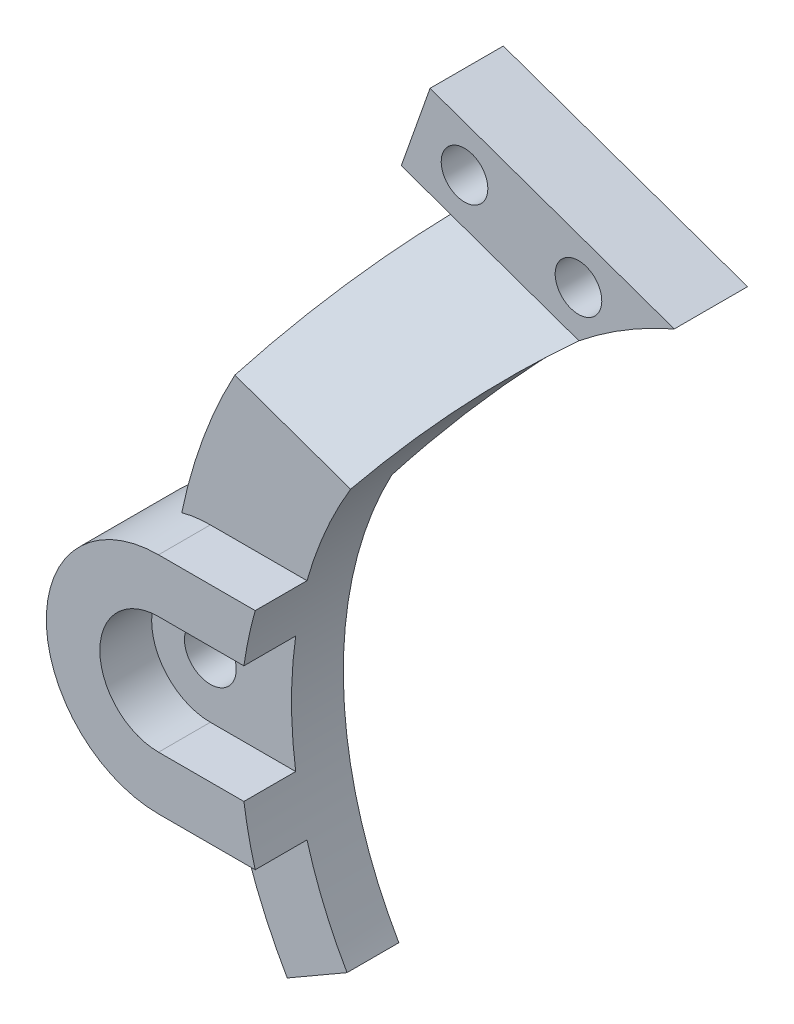
SolidWorks part; units mm, degrees
ref_plane "Plano frontal" through (0, 0, 0) normal (0, 0, 1) x (1, 0, 0)
ref_plane "Plano superior" through (0, 0, 0) normal (0, 1, 0) x (1, 0, 0)
ref_plane "Plano direito" through (0, 0, 0) normal (1, 0, 0) x (0, 0, -1)
sketch "Esboço1" plane through (0, 0, 0) normal (0, 0, 1) x (1, 0, 0)
  line L0 (0, 3.4) -> (4.9421, 3.4)
  line L1 (0, 6.5) -> (5.597, 6.5)
  line L2 (4.9421, -3.4) -> (0, -3.4)
  line L3 (0, -6.5) -> (5.597, -6.5)
  line L4 (19.1083, 22) -> (4.9662, 27)
  line L5 (4.9662, 27) -> (3.2995, 22.286)
  line L6 (3.2995, 22.286) -> (6.1544, 21.2766)
  line L7 (1.5, 0) -> (4.7, 0) construction
  line L8 (4.4513, -14) -> (7.9154, -12)
  line L9 (6.9613, 23.643) -> (13.561, 21.3096) construction
  line L10 (11.0945, 24.8333) -> (10.2611, 22.4763) construction
  circle A0 centre (0, 0) radius 1.5
  arc A1 (0, 3.4) -> (0, -3.4) centre (0, 0) ccw
  arc A2 (19.1083, 22) -> (7.9154, -12) centre (28.7, 0) ccw
  arc A3 (0, 6.5) -> (0, -6.5) centre (0, 0) ccw
  arc A4 (6.1544, 21.2766) -> (-1.6561, 6.2855) centre (28.7, 0) ccw
  arc A5 (19.1083, 22) -> (5.597, -6.5) centre (28.7, 0) ccw construction
  arc A6 (16.3108, 28.4167) -> (-1.1414, -8.3958) centre (28.7, 0) ccw construction
  arc A7 (4.4513, -14) -> (1.4649, -6.5) centre (28.7, 0) cw
  circle A8 centre (13.561, 21.3096) radius 1.35
  circle A9 centre (6.9613, 23.643) radius 1.35
  point P31 (4.1329, 24.643)
  dimension "D1" = 6.8
  dimension "D2" = 24
  dimension "D3" = 6.5
  dimension "D4" = 3
  dimension "D5" = 27
  dimension "D11" = 4
  dimension "D13" = 7
  dimension "D14" = 2.7
  dimension "D7" = 3.2
  dimension "D8" = 5
  dimension "D9" = 15
  dimension "D10" = 22
  dimension "D12" = 30
  dimension "D15" = 3
  dimension "D6" = 7
extrude "Ressalto-extrusão1" add sketch "Esboço1" along normal blind 15 contours L1 A3 L3 A2 L2 A1 L0 region at (-3.5776, 0, 0)
extrude "Ressalto-extrusão2" add sketch "Esboço1<3>" along normal blind 12 contours A2 L0 A1 L2 A0 region at (2.471, 3.2924, 0)
sketch "Esboço1<3>" plane through (0, 0, 0) normal (0, 0, 1) x (1, 0, 0) same geometry as "Esboço1"
extrude "Ressalto-extrusão3" add sketch "Esboço1<4>" along normal blind 12 contours L6 A4 L1 A2 L4 L5 | A7 L8 A2 L3 region at (6.7974, 16.5227, 0) region at (4.6114, -9.8357, 0)
sketch "Esboço1<4>" plane through (0, 0, 0) normal (0, 0, 1) x (1, 0, 0) same geometry as "Esboço1"
sketch "Esboço2" plane through (-4.0709, 1.4393, 0) normal (-0.9428, 0.3333, 0) x (0, 0, 1)
  line L0 (0, -11.7156) -> (9, -11.7156)
  line L1 (12, -11.7156) -> (0, -11.7156) construction
  line L2 (9, -11.7156) -> (9, 13.1112)
  line L3 (9, 13.1112) -> (0, 22.1112)
  line L4 (4.2426, 27.1112) -> (4.2426, 22.1112)
  line L5 (12, 27.1112) -> (0, 27.1112) construction
  line L6 (12, 22.1112) -> (0, 22.1112) construction
  line L7 (4.2426, 22.1112) -> (12, 14.3539)
  line L8 (12, 5.374) -> (12, 22.1112) construction
  line L9 (4.2426, 27.1112) -> (12, 27.1112)
  line L10 (12, 27.1112) -> (12, 14.3539)
  line L11 (0, 22.1112) -> (0, -11.7156)
  dimension "D1" = 3
  dimension "D2" = 45
  dimension "D3" = 3
extrude "Corte-extrusão1" cut sketch "Esboço2" against normal through all both and the other way through all
